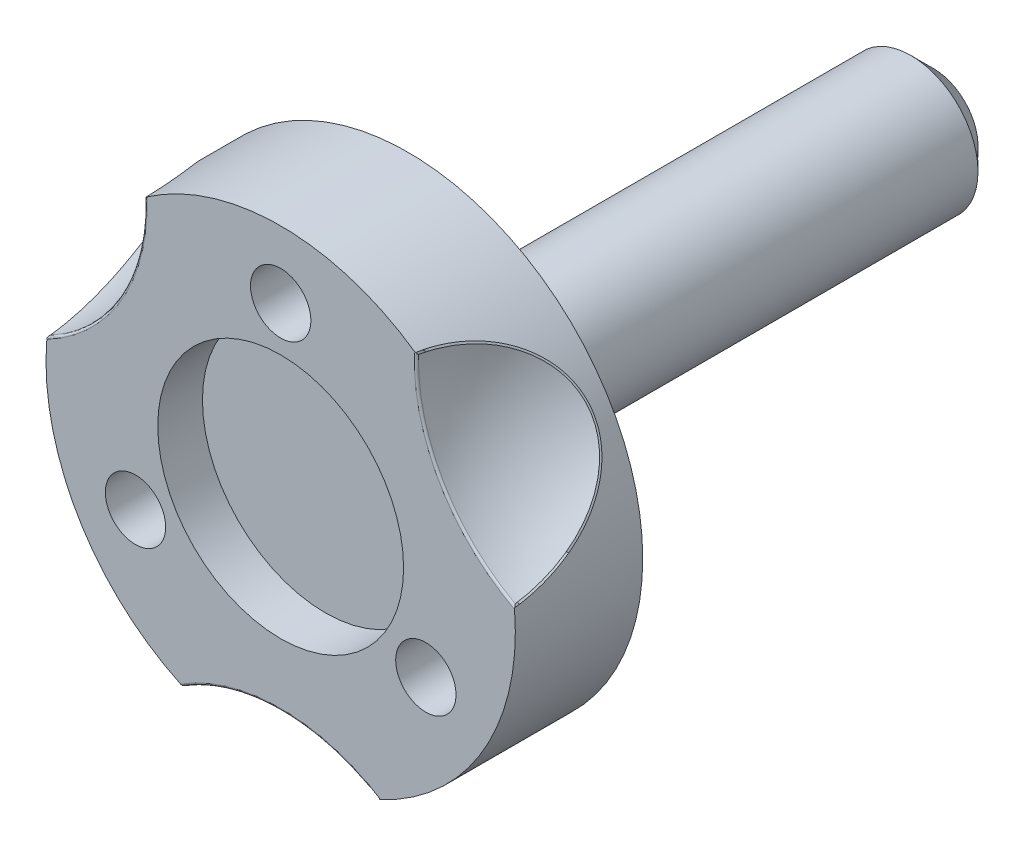
SolidWorks part; units mm, degrees
ref_plane "Ön Düzlem" through (0, 0, 0) normal (0, 0, 1) x (1, 0, 0)
ref_plane "Üst Düzlem" through (0, 0, 0) normal (0, 1, 0) x (1, 0, 0)
ref_plane "Sağ Düzlem" through (0, 0, 0) normal (1, 0, 0) x (0, 0, -1)
sketch "Çizim1" plane through (0, 0, 0) normal (0, 0, 1) x (1, 0, 0)
  circle A0 centre (0, 0) radius 10.5
  circle A1 centre (0, 0) radius 7.5 construction
  circle A2 centre (0, 7.5) radius 1.35
  circle A3 centre (0, 7.5) radius 2.4
  circle A4 centre (6.4952, -3.75) radius 2.4
  circle A5 centre (6.4952, -3.75) radius 1.35
  circle A6 centre (-6.4952, -3.75) radius 2.4
  circle A7 centre (-6.4952, -3.75) radius 1.35
  circle A8 centre (0, 0) radius 5.5
  dimension "D1" = 3
extrude "Yükseklik-Ekstrüzyon1" add sketch "Çizim1" along normal blind 6.5 contours A0 A8 A3 A4 A6 | A3 A8 A6 A4 | A8 A6 A7 | A8 A4 A5 | A4 A8 | A6 A8 | A2 | A3 region at (-10.203, 0, 0) region at (0, 7.5, 0) region at (0, 0, 0) region at (-4.8219, -2.7839, 0) region at (-4.6036, -2.6579, 0) region at (4.6036, -2.6579, 0) region at (7.6274, -1.7112, 0)
extrude "Kes-Ekstrüzyon1" cut sketch "Çizim1<3>" along normal blind 2.8 contours A8 A4 A5 | A4 A8 | A6 | A3 region at (4.6036, -2.6579, 0) region at (7.6274, -1.7112, 0)
sketch "Çizim1<3>" plane through (0, 0, 0) normal (0, 0, 1) x (1, 0, 0) same geometry as "Çizim1"
extrude "Kes-Ekstrüzyon2" cut sketch "Çizim1<4>" against normal blind 2.8 from surface contours A8 starting at face at (10.5, 0, 6.5)
sketch "Çizim1<4>" plane through (0, 0, 0) normal (0, 0, 1) x (1, 0, 0) same geometry as "Çizim1"
sketch "Çizim2" plane through (0, 0, 0) normal (0, 0, -1) x (-1, 0, 0)
  circle A0 centre (0, 0) radius 3
extrude "Yükseklik-Ekstrüzyon2" add sketch "Çizim2" along normal blind 23.5
fillet "Radyus1" radius 0.4 1 edges at (3, 0, 0)
chamfer "Pah1" distance 1 angle 45 1 edges at (-3, 0, -23.5)
sketch "Çizim4" plane through (0, 0, 6.5) normal (0, 0, 1) x (1, 0, 0)
  line L0 (0, 0) -> (-6.4724, -3.7895) construction
  line L1 (-6.4724, -3.7895) -> (-15.102, -8.842) construction
  line L2 (-7.5, 0) -> (-7.5, -15.8114) construction
  line L3 (7.5, 0) -> (7.5, -15.8114) construction
  line L4 (-7.5, 0) -> (-8.3072, -15.4026) construction
  line L5 (7.5, 0) -> (8.3072, -15.4026) construction
  line L6 (0, 0) -> (-11.7442, -12.974) construction
  line L7 (0, 0) -> (-17.0618, -3.8915) construction
  line L8 (-15.6575, -3.0693) -> (-17.0618, -3.8915)
  line L9 (-10.3398, -12.1518) -> (-11.7442, -12.974)
  line L10 (5.1707, 15.0944) -> (5.1608, 16.7217)
  line L11 (-5.3538, 15.0304) -> (-5.3637, 16.6577)
  line L12 (10.4868, -12.0252) -> (11.901, -12.8302)
  line L13 (15.6937, -2.8787) -> (17.1079, -3.6838)
  circle A1 centre (0, 0) radius 17.5
  circle A2 centre (0, 0) radius 7.5 construction
  arc A8 (7.5, -15.8114) -> (7.5, -15.6891) centre (0, -15.7502) ccw
  arc A9 (-8.2512, -15.4327) -> (8.2512, -15.4327) centre (0, -16.5807) cw
  arc A10 (-7.5, -15.6891) -> (-7.5, -15.8114) centre (0, -15.7502) ccw
  arc A11 (-9.2395, 14.8621) -> (-17.4907, 0.5706) centre (-14.3593, 8.2904) cw
  arc A12 (17.4907, 0.5706) -> (9.2395, 14.8621) centre (14.3593, 8.2904) cw
  arc A13 (-15.6575, -3.0693) -> (-10.3398, -12.1518) centre (-13.6489, -7.9912) cw
  arc A14 (5.1707, 15.0944) -> (-5.3538, 15.0304) centre (-0.0961, 15.8159) cw
  arc A15 (10.4868, -12.0252) -> (15.6937, -2.8787) centre (13.745, -7.8247) cw
  arc A16 (8.106, 13.7946) -> (5.1704, 15.1416) centre (0, 0) ccw
  arc A17 (5.0884, 14.641) -> (-5.266, 14.578) centre (0, 0) ccw
  arc A18 (-7.783, 13.4043) -> (-15.5, 0.0381) centre (0, 0) ccw
  arc A19 (-15.2237, -2.9138) -> (-9.9919, -11.8495) centre (0, 0) ccw
  arc A20 (-7.717, -13.4424) -> (7.717, -13.4424) centre (0, 0) ccw
  arc A21 (10.1352, -11.7272) -> (15.258, -2.7285) centre (0, 0) ccw
  arc A22 (15.5, 0.0381) -> (7.783, 13.4043) centre (0, 0) ccw
  arc A23 (-5.3541, 15.0776) -> (-8.106, 13.7946) centre (0, 0) ccw
  arc A24 (-15.9995, 0.1227) -> (-15.6982, -3.0931) centre (0, 0) ccw
  arc A25 (-10.3805, -12.1756) -> (-7.8935, -13.9174) centre (0, 0) ccw
  arc A26 (7.8935, -13.9174) -> (10.5278, -12.0485) centre (0, 0) ccw
  arc A27 (15.7346, -2.902) -> (15.9995, 0.1227) centre (0, 0) ccw
  circle A29 centre (0, 7.5) radius 1.25
  circle A30 centre (6.4952, -3.75) radius 1.25
  circle A31 centre (-6.4952, -3.75) radius 1.25
  point P2 (-9.0613, -5.3052)
  point P8 (0, -8.25)
  point P17 (-8.3072, -15.4026)
  circle M63 centre (0, 0) radius 5.5
  circle M64 centre (0, 0) radius 10.5
  circle M65 centre (-6.4952, -3.75) radius 1.35
  circle M66 centre (6.4952, -3.75) radius 1.35
  circle M67 centre (0, 7.5) radius 1.35
  dimension "D1" = 3
  dimension "D2" = 8.25
  dimension "D4" = 35
  dimension "D5" = 15
  dimension "D6" = 3
  dimension "D10" = 7.5
  dimension "D11" = 2.5
  dimension "D3" = 3
  dimension "3" = 3
  dimension "D7" = 17.5
  dimension "D8" = 3
  dimension "D9" = 3
extrude "Kes-Ekstrüzyon3" cut sketch "Çizim4" against normal blind 0.8 contours L13 A27 A12 A9 A26 L12 A15 M64 | A12 A11 A9 M64 M66 M67 M65 M63 | L9 A25 A9 A11 A24 L8 A13 M64 | L11 A23 A11 A12 A16 L10 A14 M64 region at (-15.6874, -3.0649, 6.5) region at (-6.8934, 3.9799, 6.5) region at (-7.8068, 13.7134, 6.5) region at (8.8677, -5.6577, 6.5)
sketch "Çizim5" plane through (0, 0, 6.5) normal (0, 0, 1) x (1, 0, 0)
  line L0 (-14.3593, 8.2904) -> (-2.5018, 19.5901)
  arc A0 (-15.5, 0.0381) -> (-7.783, 13.4043) centre (-14.3593, 8.2904) ccw
  arc A1 (-17.4907, 0.5706) -> (-9.2395, 14.8621) centre (-14.3593, 8.2904) ccw construction
  arc A2 (-7.783, 13.4043) -> (-15.5, 0.0381) centre (0, 0) ccw
  point P3 (-7.1447, 4.125)
revolve "Kes-Döndür1" cut sketch "Çizim5" angle 360 about L0 region at (-10.9559, 6.3254, 6.5) region at (-8.1421, 4.7009, 6.5)
pattern_circular "Dairesel Kaplama1" count 3 over 360 about axis through (0, 0, 5.7) along (0, 0, 1) of "Kes-Döndür1"
sketch "Çizim6" plane through (0, 0, 5.7) normal (0, 0, 1) x (1, 0, 0)
  circle A0 centre (-0.2348, -0.1639) radius 19.1932
extrude "Kes-Ekstrüzyon4" cut sketch "Çizim6" along normal blind 10
fillet "Radyus2" radius 0.1 6 edges at (9.2415, 4.9844, 0.8185) (7.1781, 4.1443, 5.7) (0, -8.2885, 5.7) (-0.3042, -10.4956, 0.8185) (-7.1781, 4.1443, 5.7) (-8.9374, 5.5112, 0.8185)
